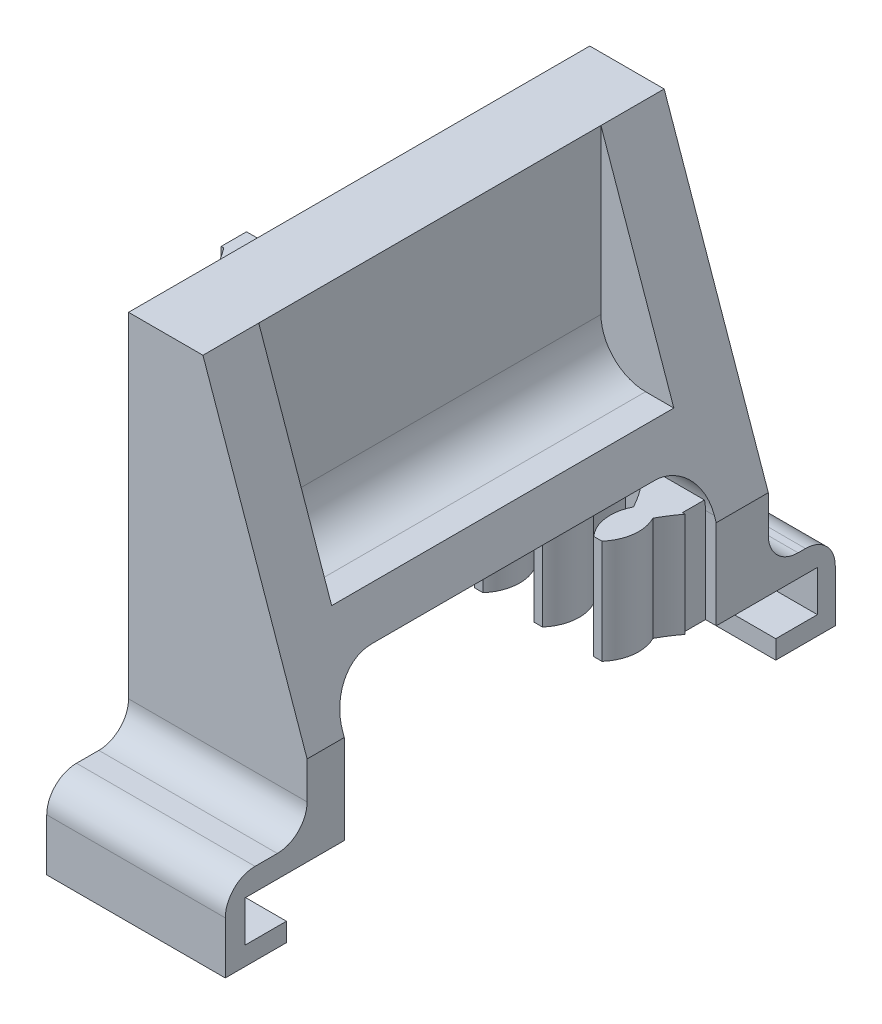
SolidWorks part; units mm, degrees
ref_plane "Front Plane" through (0, 0, 0) normal (0, 0, 1) x (1, 0, 0)
ref_plane "Top Plane" through (0, 0, 0) normal (0, 1, 0) x (1, 0, 0)
ref_plane "Right Plane" through (0, 0, 0) normal (1, 0, 0) x (0, 0, -1)
sketch "Sketch1" plane through (0, 0, 0) normal (0, 0, 1) x (1, 0, 0)
  line L0 (0, 0) -> (0, -30)
  line L1 (0, -30) -> (12, -30)
  line L2 (12, -30) -> (12, -20)
  line L3 (12, -20) -> (5, 0)
  line L4 (5, 0) -> (0, 0)
  dimension "D1" = 30
  dimension "D2" = 12
  dimension "D3" = 10
  dimension "D4" = 5
extrude "Boss-Extrude1" add sketch "Sketch1" against normal blind 31
sketch "Sketch4" plane through (0, 0, 0) normal (-1, 0, 0) x (0, 0, 1)
  line L0 (-31, 0) -> (-31, -30) construction
  line L1 (-27.5, -16.6434) -> (-2.5, -16.6434)
  line L2 (-27.5, -16.6434) -> (-27.5, -31.6434)
  line L3 (-27.5, -31.6434) -> (-2.5, -31.6434)
  line L4 (-2.5, -16.6434) -> (-2.5, -31.6434)
  point P4 (-27.5, -24.1434)
  dimension "D1" = 25
  dimension "D2" = 15
  dimension "D3" = 3.5
extrude "Cut-Extrude2" cut sketch "Sketch4" against normal blind 25 contours L2 L1 L4 L3
ref_plane "Plane1" through (0, 0, -15.25) normal (0, 0, 1) x (1, 0, 0)
sketch "Sketch6" plane through (0, 0, -15.25) normal (0, 0, 1) x (1, 0, 0)
  line L0 (5, 0) -> (5, -14)
  line L1 (5, -14) -> (9.9, -14)
  line L2 (12, -20) -> (5, 0) construction
  line L3 (9.9, -14) -> (5, 0)
  dimension "D1" = 14
extrude "Cut-Extrude4" cut sketch "Sketch6" against normal mid plane 23
ref_plane "Plane3" through (0, -26, 0) normal (0, 1, 0) x (1, 0, 0)
sketch "Sketch7" plane through (0, -26, 0) normal (0, 1, 0) x (1, 0, 0)
  line L0 (11.2768, 27.65) -> (-19.7232, 27.65)
  line L62 (-16.5, 15.25) -> (16.5, 15.25) construction
  line L162 (11.2768, 27.65) -> (11.2768, 25.95)
  line L172 (-19.7232, 25.95) -> (-19.7232, 27.65)
  line L243 (11.2768, 25.95) -> (-19.7232, 25.95)
  dimension "D2" = 31
  dimension "D3" = 1.7
  dimension "D7" = 12.4
extrude "Boss-Extrude3" add sketch "Sketch7" along normal blind 7
sketch "Sketch10" plane through (0, -26, 0) normal (0, 1, 0) x (1, 0, 0)
  line L1 (9.9522, 21.5888) -> (9.9522, 23.4692) construction
  line L2 (10.2298, 21.5888) -> (9.6745, 21.5888)
  line L4 (-19.7232, 25.95) -> (11.2768, 25.95) construction
  line L5 (8.4522, 25.95) -> (11.4522, 25.95)
  arc A0 (10.2298, 21.5888) -> (10.6038, 24.6369) centre (8.1908, 23.386) ccw
  arc A1 (10.6038, 24.6369) -> (11.4522, 25.95) centre (19.0749, 20.0948) cw
  arc A2 (9.3005, 24.6369) -> (8.4522, 25.95) centre (0.8294, 20.0948) ccw
  arc A3 (9.6745, 21.5888) -> (9.3005, 24.6369) centre (11.7135, 23.386) cw
  point P7 (8.7243, 24.6306)
  point P15 (9.3005, 24.6369)
  dimension "D1" = 3
extrude "Boss-Extrude4" add sketch "Sketch10" along normal blind 7
pattern_linear "LPattern1" count 8 spacing 4 along (-1, 0, 0) of "Boss-Extrude4"
sketch "Sketch11" plane through (0, 0, -31) normal (0, 0, -1) x (-1, 0, 0)
  line L0 (-12, -30) -> (-12, -20) construction
  line L1 (-12, -24.5) -> (0, -24.5)
  line L2 (-12, -24.5) -> (-12, -30)
  line L3 (-12, -30) -> (0, -30)
  line L4 (0, -24.5) -> (0, -30)
  dimension "D1" = 5.5
extrude "Boss-Extrude5" add sketch "Sketch11" along normal blind 4.5
fillet "Fillet5" radius 3 3 edges at (5, -14, -15.25) (5.4126, -16.6434, -2.5) (5.4126, -16.6434, -27.5)
sketch "Sketch12" plane through (0, 0, 0) normal (0, 0, 1) x (1, 0, 0)
  line L0 (12, -30) -> (12, -20) construction
  line L1 (0, -30) -> (12, -30)
  line L2 (0, -30) -> (0, -24.5)
  line L3 (0, -24.5) -> (12, -24.5)
  line L4 (12, -30) -> (12, -24.5)
  dimension "D1" = 5.5
extrude "Boss-Extrude6" add sketch "Sketch12" along normal blind 5.5
sketch "Sketch13" plane through (0, 0, 0) normal (-1, 0, 0) x (0, 0, 1)
  line L0 (-34.3, -26) -> (-27.5, -26)
  line L1 (-27.5, -26) -> (-27.5, -32.0691)
  line L2 (-27.5, -32.0691) -> (-31.5, -32.0691)
  line L3 (-31.5, -32.0691) -> (-31.5, -28.75)
  line L4 (-31.5, -28.75) -> (-34.3, -28.75)
  line L5 (-34.3, -28.75) -> (-34.3, -26)
  line L6 (-15.0561, -22.9316) -> (-15.0561, -37.9805) construction
  line L7 (-2.5, -30) -> (5.5, -30) construction
  line L9 (-27.5, -26) -> (-27.5, -30) construction
  line L12 (1.3878, -28.75) -> (4.1878, -28.75)
  line L13 (1.3878, -32.0691) -> (1.3878, -28.75)
  line L14 (-2.6122, -32.0691) -> (1.3878, -32.0691)
  line L15 (-2.6122, -26) -> (-2.6122, -32.0691)
  line L16 (4.1878, -26) -> (-2.6122, -26)
  line L17 (4.1878, -28.75) -> (4.1878, -26)
  dimension "D1" = 6.8
  dimension "D2" = 0
  dimension "D3" = 4
  dimension "D4" = 2.75
  dimension "D5" = 4
extrude "Cut-Extrude5" cut sketch "Sketch13" against normal up to surface (12 mm away) up to face at (12, -24.8333, 1)
fillet "Fillet6" radius 2 4 edges at (6, -24.5, -35.5) (6, -24.5, -31) (6, -24.5, 5.5) (6, -24.5, 0)
